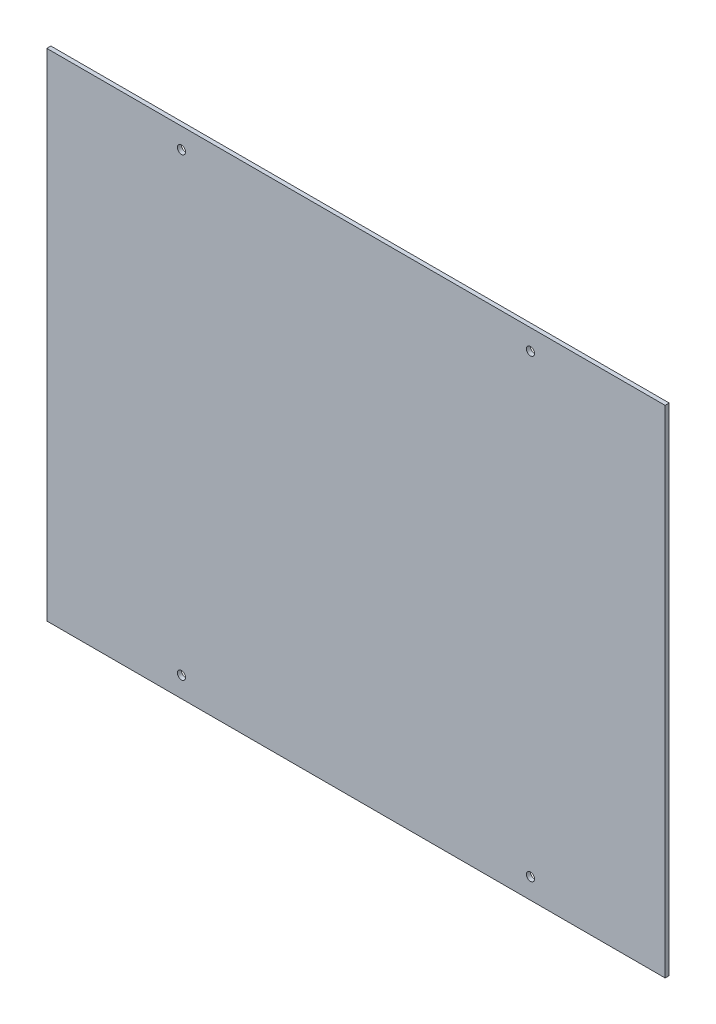
SolidWorks part; units mm, degrees
ref_plane "Front Plane" through (0, 0, 0) normal (0, 0, 1) x (1, 0, 0)
ref_plane "Top Plane" through (0, 0, 0) normal (0, 1, 0) x (1, 0, 0)
ref_plane "Right Plane" through (0, 0, 0) normal (1, 0, 0) x (0, 0, -1)
sketch "Sketch1" plane through (0, 0, 0) normal (0, 0, 1) x (1, 0, 0)
  line L0 (0, 0) -> (-206.9982, 0) construction
  line L1 (151.5, -121.5) -> (-151.5, -121.5)
  line L2 (151.5, -121.5) -> (151.5, 121.5)
  line L3 (151.5, 121.5) -> (-151.5, 121.5)
  line L4 (-151.5, -121.5) -> (-151.5, 121.5)
  line L5 (151.5, -121.5) -> (-151.5, 121.5) construction
  line L6 (151.5, 121.5) -> (-151.5, -121.5) construction
  line L7 (139.0309, -111.5) -> (-139.0309, -111.5) construction
  line L8 (139.0309, -111.5) -> (139.0309, 111.5) construction
  line L9 (139.0309, 111.5) -> (-139.0309, 111.5) construction
  line L10 (-139.0309, -111.5) -> (-139.0309, 111.5) construction
  line L11 (139.0309, -111.5) -> (-139.0309, 111.5) construction
  line L12 (139.0309, 111.5) -> (-139.0309, -111.5) construction
  circle A0 centre (-85.5, 111.5) radius 2
  circle A1 centre (85.5, 111.5) radius 2
  circle A2 centre (85.5, -111.5) radius 2
  circle A3 centre (-85.5, -111.5) radius 2
  point P0 (0, 0)
  point P5 (0, 0)
  dimension "D4" = 4
  dimension "D5" = 4
  dimension "D1" = 303
  dimension "D2" = 243
  dimension "D3" = 10
  dimension "D6" = 66
  dimension "D7" = 66
extrude "Boss-Extrude1" add sketch "Sketch1" along normal blind 2
